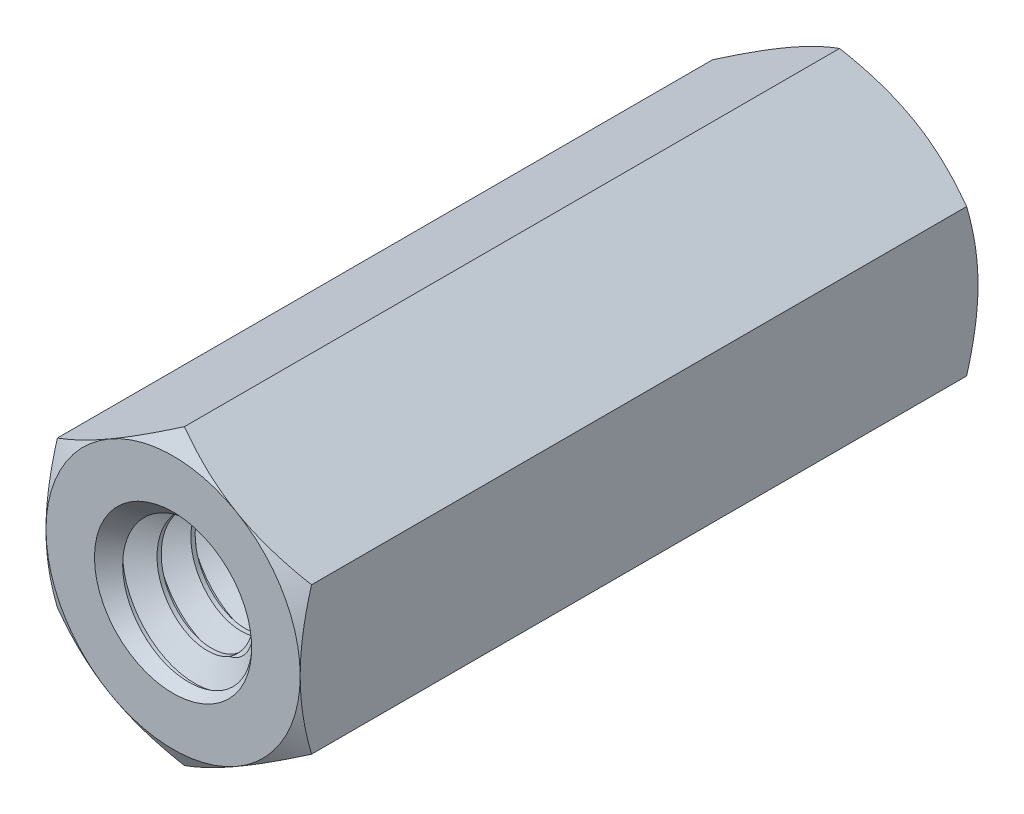
SolidWorks part; units mm, degrees
material "Brass"
ref_plane "Front Plane" through (0, 0, 0) normal (0, 0, 1) x (1, 0, 0)
ref_plane "Top Plane" through (0, 0, 0) normal (0, 1, 0) x (1, 0, 0)
ref_plane "Right Plane" through (0, 0, 0) normal (1, 0, 0) x (0, 0, -1)
sketch "Sketch3" plane through (0, 0, 0) normal (1, 0, 0) x (0, 0, -1)
  line L0 (-6.35, 0) -> (6.35, 0) construction
  line L1 (0, 2.3813) -> (0, -2.3813) construction
  line L2 (-6.35, 1.4224) -> (-6.35, -1.4224) construction
  point P2 (-9.525, 0)
  point P3 (9.525, 0)
  dimension "Length" = 12.7
  dimension "Min Thread Length" = 15.875
  dimension "D1" = 15.875
  dimension "Thread Dia" = 2.8448
  dimension "Hex" = 4.7625
sketch "Sketch1" plane through (0, 0, 0) normal (0, 0, 1) x (1, 0, 0)
  line L1 (0, 2.7496) -> (-2.3813, 1.3748)
  line L2 (-2.3813, 1.3748) -> (-2.3813, -1.3748)
  line L3 (-2.3813, -1.3748) -> (0, -2.7496)
  line L4 (0, -2.7496) -> (2.3813, -1.3748)
  line L5 (2.3813, -1.3748) -> (2.3812, 1.3748)
  line L6 (2.3812, 1.3748) -> (0, 2.7496)
  circle A0 centre (0, 0) radius 2.3813 construction
  circle A1 centre (0, 0) radius 1.4224
extrude "Extrude1" add sketch "Sketch1" along normal up to vertex (6.35 mm away) and the other way up to vertex (6.35 mm away) up to point (0, 0, 6.35) other way up to point (0, 0, -6.35)
sketch "Sketch11" plane through (0, 0, -6.35) normal (0, 0, -1) x (-1, 0, 0)
  circle A0 centre (0, 0) radius 1.4224 construction
  circle A1 centre (0, 0) radius 1.4224
curve "Helix/Spiral1" pitch 0.635 height 13.335 radius 1.4224 centre (0, 0, -6.35) axis (0, 0, 1) start towards (0, 1, 0) parameters "Pitch"=0.635
sketch "Sketch12" plane through (0, 0, 0) normal (1, 0, 0) x (0, 0, -1)
  line L0 (6.9056, 1.4224) -> (6.35, 1.4224)
  line L1 (6.9056, 1.4224) -> (6.6675, 1.01)
  line L2 (6.6675, 1.01) -> (6.5881, 1.01)
  line L3 (6.5881, 1.01) -> (6.35, 1.4224)
  line L4 (6.6278, 1.01) -> (6.6278, 1.4224) construction
  line L5 (6.7866, 1.2162) -> (6.4691, 1.2162) construction
  dimension "D1" = 0.0794
  dimension "D2" = 0.3175
  dimension "D3" = 60
sweep "Sweep1" add profiles "Sketch12" path "Helix/Spiral1"
sketch "Sketch6" plane through (0, 0, -6.35) normal (0, 0, -1) x (-1, 0, 0)
  line L6 (0, 2.7496) -> (-2.3812, 1.3748)
  line L7 (-2.3812, 1.3748) -> (-2.3813, -1.3748)
  line L8 (-2.3813, -1.3748) -> (0, -2.7496)
  line L9 (0, -2.7496) -> (2.3813, -1.3748)
  line L10 (2.3813, -1.3748) -> (2.3813, 1.3748)
  line L11 (2.3813, 1.3748) -> (0, 2.7496)
  line L12 (0, 2.7496) -> (-2.3812, 1.3748)
  line L13 (-2.3812, 1.3748) -> (-2.3813, -1.3748)
  line L14 (-2.3813, -1.3748) -> (0, -2.7496)
  line L15 (0, -2.7496) -> (2.3813, -1.3748)
  line L16 (2.3813, -1.3748) -> (2.3813, 1.3748)
  line L17 (2.3813, 1.3748) -> (0, 2.7496)
  dimension "D1" = 0
extrude "Extrude2" cut sketch "Sketch6" along normal through all
sketch "Sketch7" plane through (0, 0, -6.35) normal (0, 0, -1) x (-1, 0, 0)
  circle A2 centre (0, 0) radius 1.4732
  circle A3 centre (0, 0) radius 1.4732
  dimension "D1" = 0.0508
extrude "Extrude3" cut sketch "Sketch7" against normal through all draft 43
sketch "Sketch8" plane through (0, 0, -6.35) normal (0, 0, -1) x (-1, 0, 0)
  circle A0 centre (0, 0) radius 2.3813 construction
  circle A1 centre (0, 0) radius 2.3813
extrude "Extrude4" cut sketch "Sketch8" against normal through all draft 60 flip side to cut
mirror "Mirror1" about plane through (0, 0, 0) normal (0, 0, 1) of "Extrude2", "Extrude3", "Extrude4"
sketch "Sketch9" [suppressed] plane through (0, 0, 0) normal (1, 0, 0) x (0, 0, -1)
  line L1 (-22.225, 3.2258) -> (22.225, 3.2258)
  line L2 (-22.225, 3.2258) -> (-22.225, 0)
  line L3 (-22.225, 0) -> (22.225, 0)
  line L4 (22.225, 3.2258) -> (22.225, 0)
  line L7 (-38.1, 0) -> (38.1, 0) construction
revolve "Revolve" [suppressed] add sketch "Sketch9" angle 360 about L0
sketch "Sketch10" [suppressed] plane through (0, 0, 0) normal (1, 0, 0) x (0, 0, -1)
  line L0 (38.1, 3.175) -> (22.225, 3.175)
  line L1 (-38.1, 3.175) -> (-22.225, 3.175)
  line L2 (22.225, 3.175) -> (22.225, -3.175)
  line L3 (-38.1, -3.2258) -> (-22.225, -3.2258)
  line L4 (-22.225, 3.175) -> (-22.225, -3.2258)
  line L5 (22.225, -3.175) -> (38.1, -3.175)
equation "\"D1@Sketch3\" = \"Min Thread Length@Sketch3\""
equation "\"D3@Helix/Spiral1\" = \"Length@Sketch3\"+\"Pitch@Helix/Spiral1\""
equation "\"D1@Sketch12\" = \"Pitch@Helix/Spiral1\"*.125"
equation "\"D2@Sketch12\" = \"Pitch@Helix/Spiral1\"*.5"
